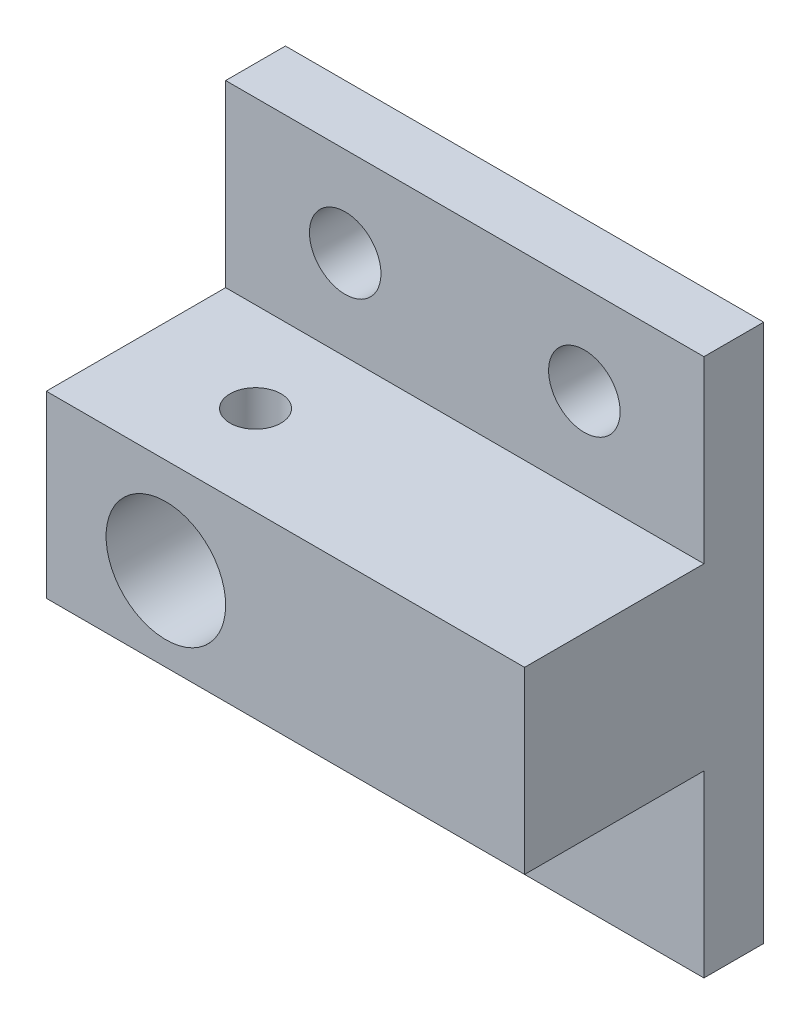
SolidWorks part; units mm, degrees
ref_plane "Front Plane" through (0, 0, 0) normal (0, 0, 1) x (1, 0, 0)
ref_plane "Top Plane" through (0, 0, 0) normal (0, 1, 0) x (1, 0, 0)
ref_plane "Right Plane" through (0, 0, 0) normal (1, 0, 0) x (0, 0, -1)
sketch "Sketch1" plane through (0, 0, 0) normal (0, 0, 1) x (1, 0, 0)
  line L1 (-12.7, -14.2875) -> (12.7, -14.2875)
  line L2 (-12.7, -14.2875) -> (-12.7, 14.2875)
  line L3 (-12.7, 14.2875) -> (12.7, 14.2875)
  line L4 (12.7, -14.2875) -> (12.7, 14.2875)
  line L5 (-12.7, -14.2875) -> (12.7, 14.2875) construction
  line L6 (-12.7, 14.2875) -> (12.7, -14.2875) construction
  point P0 (0, 0)
  dimension "D1" = 25.4
  dimension "D2" = 28.575
extrude "Boss-Extrude1" add sketch "Sketch1" along normal blind 12.7
sketch "Sketch3" plane through (0, 0, 12.7) normal (0, 0, 1) x (1, 0, 0)
  line L0 (0, -55) -> (0, 55) construction
  line L1 (-12.7, 4.7625) -> (12.7, 4.7625)
  line L2 (-12.7, 4.7625) -> (-12.7, 14.2875)
  line L3 (-12.7, 14.2875) -> (12.7, 14.2875)
  line L4 (12.7, 4.7625) -> (12.7, 14.2875)
  line L5 (-12.7, 4.7625) -> (12.7, 14.2875) construction
  line L6 (-12.7, 14.2875) -> (12.7, 4.7625) construction
  line L9 (-12.7, -4.7625) -> (12.7, -4.7625)
  line L10 (-12.7, -4.7625) -> (-12.7, -14.2875)
  line L11 (-12.7, -14.2875) -> (12.7, -14.2875)
  line L12 (12.7, -4.7625) -> (12.7, -14.2875)
  line L13 (-12.7, -4.7625) -> (12.7, -14.2875) construction
  line L14 (-12.7, -14.2875) -> (12.7, -4.7625) construction
  point P0 (0, 9.525)
  point P5 (0, -9.525)
  line M2 (12.7, -14.2875) -> (12.7, 14.2875)
  line M4 (-12.7, 14.2875) -> (-12.7, -14.2875)
  line M5 (-12.7, -14.2875) -> (12.7, -14.2875)
  dimension "D1" = 9.525
  dimension "D2" = 9.525
extrude "Cut-Extrude1" cut sketch "Sketch3" against normal blind 9.525 contours L9 M4 M5 M2 | L1 L4 L3 L2 region at (0, -9.525, 12.7)
sketch "Sketch2" plane through (0, 0, 12.7) normal (0, 0, 1) x (1, 0, 0)
  line L2 (-12.7, 4.7625) -> (-12.7, -4.7625) construction
  line L3 (-12.7, 4.7625) -> (12.7, 4.7625) construction
  circle A0 centre (-6.35, -0.3175) radius 3.175
  point P7 (0, 0)
  point P8 (0, 0)
  point P9 (0, 0)
  dimension "D1" = 6.35
  dimension "D2" = 6.35
  dimension "D3" = 5.08
extrude "Cut-Extrude2" cut sketch "Sketch2" against normal through all contours A0
sketch "Sketch4" plane through (0, 4.7625, 0) normal (0, 1, 0) x (1, 0, 0)
  line L0 (-12.7, -3.175) -> (-12.7, -12.7) construction
  point P0 (-6.35, -7.9375)
  point P3 (-12.7, -7.9375)
  point P4 (0, 0)
  dimension "D1" = 6.35
hole_wizard "#6-32 Tapped Hole1" positions "Sketch5" profile "Sketch7" tap size "#6-32" standard "ANSI Inch" end condition up to next
sketch "Sketch5" plane through (0, 4.7625, 0) normal (0, 1, 0) x (1, 0, 0)
  point P0 (-6.35, -7.9375)
sketch "Sketch7" plane through (-6.35, 4.7625, 7.9375) normal (1, 0, 0) x (0, 0, 1)
  line L0 (0, 0) -> (0, 1.905)
  line L1 (0, 1.905) -> (1.3525, 1.905)
  line L2 (1.3525, 1.905) -> (1.3525, 0)
  line L5 (1.3525, 0) -> (0, 0)
  line L11 (0, -6.35) -> (0, 107.95) construction
  dimension "Thru Tap Drill Dia." = 2.7051
  dimension "Thru Tap Drill Depth" = 1.905
cosmetic thread "Hole Thread1" parameters "D2"=3.5052
sketch "Sketch8" plane through (0, 0, 3.175) normal (0, 0, 1) x (1, 0, 0)
  line L0 (-12.7, 4.7625) -> (-12.7, 14.2875) construction
  line L1 (-6.35, 9.525) -> (6.35, 9.525) construction
  line L2 (0, -55) -> (0, 55) construction
  line L4 (-12.7, -4.7625) -> (-12.7, -14.2875) construction
  circle A0 centre (-6.35, -0.3175) radius 3.175 construction
  point P0 (-6.35, 9.525)
  point P1 (6.35, 9.525)
  point P2 (0, 9.525)
  point P6 (-12.7, 9.525)
  point P10 (-6.35, -8.5725)
  point P14 (0, 0)
  point P17 (0, 0)
  dimension "D1" = 12.7
  dimension "D2" = 6.35
  dimension "D3" = 8.255
hole_wizard "#6 Clearance Hole1" positions "Sketch9" profile "Sketch11" hole size "#6" standard "ANSI Inch" end condition up to next
sketch "Sketch9" plane through (0, 0, 3.175) normal (0, 0, 1) x (1, 0, 0)
  point P0 (-6.35, 9.525)
  point P3 (6.35, 9.525)
  point P6 (-6.35, -8.5725)
sketch "Sketch11" plane through (-6.35, 9.525, 3.175) normal (1, 0, 0) x (0, -1, 0)
  line L0 (0, 0) -> (0, 3.175)
  line L1 (0, 3.175) -> (1.8986, 3.175)
  line L2 (1.8986, 3.175) -> (1.8986, 0)
  line L5 (1.8986, 0) -> (0, 0)
  line L11 (0, -6.35) -> (0, 107.95) construction
  dimension "Thru Hole Dia." = 3.7973
  dimension "Thru Hole Depth" = 3.175
